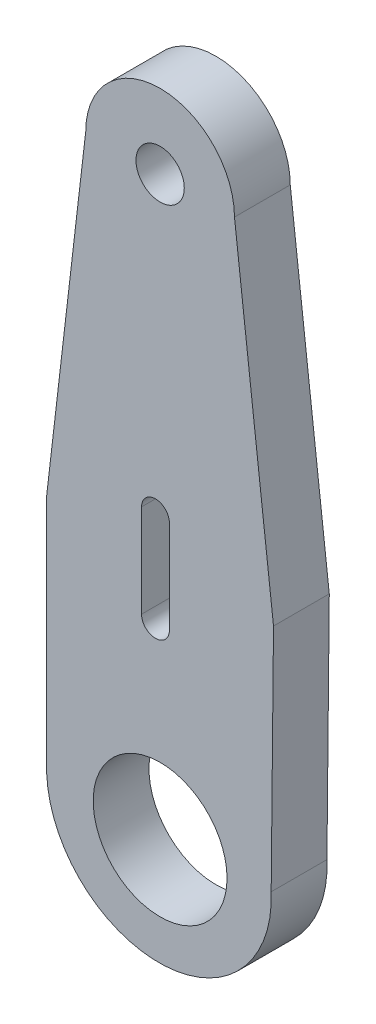
SolidWorks part; units mm, degrees
ref_plane "Front Plane" through (0, 0, 0) normal (0, 0, 1) x (1, 0, 0)
ref_plane "Top Plane" through (0, 0, 0) normal (0, 1, 0) x (1, 0, 0)
ref_plane "Right Plane" through (0, 0, 0) normal (1, 0, 0) x (0, 0, -1)
sketch "Model" plane through (0, 0, 0) normal (0, 0, 1) x (1, 0, 0)
  line L0 (54.4, 32.325) -> (54.4, 38.325)
  line L1 (66.6, 38.325) -> (66.4744, 25.8791)
  line L2 (64.5, 56.3249) -> (66.6, 38.325)
  line L3 (56.5, 56.3249) -> (54.4, 38.325)
  line L4 (59.5, 35.3249) -> (59.5, 40.3249)
  line L5 (61, 40.3249) -> (61, 35.3249)
  line L6 (54.4, 32.325) -> (54.4, 25.325)
  circle A0 centre (60.5, 56.3249) radius 1.3
  circle A1 centre (60.5001, 25.325) radius 3.6
  arc A2 (59.5, 40.3249) -> (61, 40.3249) centre (60.25, 40.3249) cw
  arc A3 (59.5, 35.3249) -> (61, 35.3249) centre (60.25, 35.3249) ccw
  arc A4 (64.5, 56.3249) -> (56.5, 56.3249) centre (60.5, 56.3249) ccw
  arc A5 (54.4, 25.325) -> (66.4744, 25.8791) centre (60.4372, 25.6021) ccw
extrude "Boss-Extrude1" add sketch "Model" along normal blind 3
